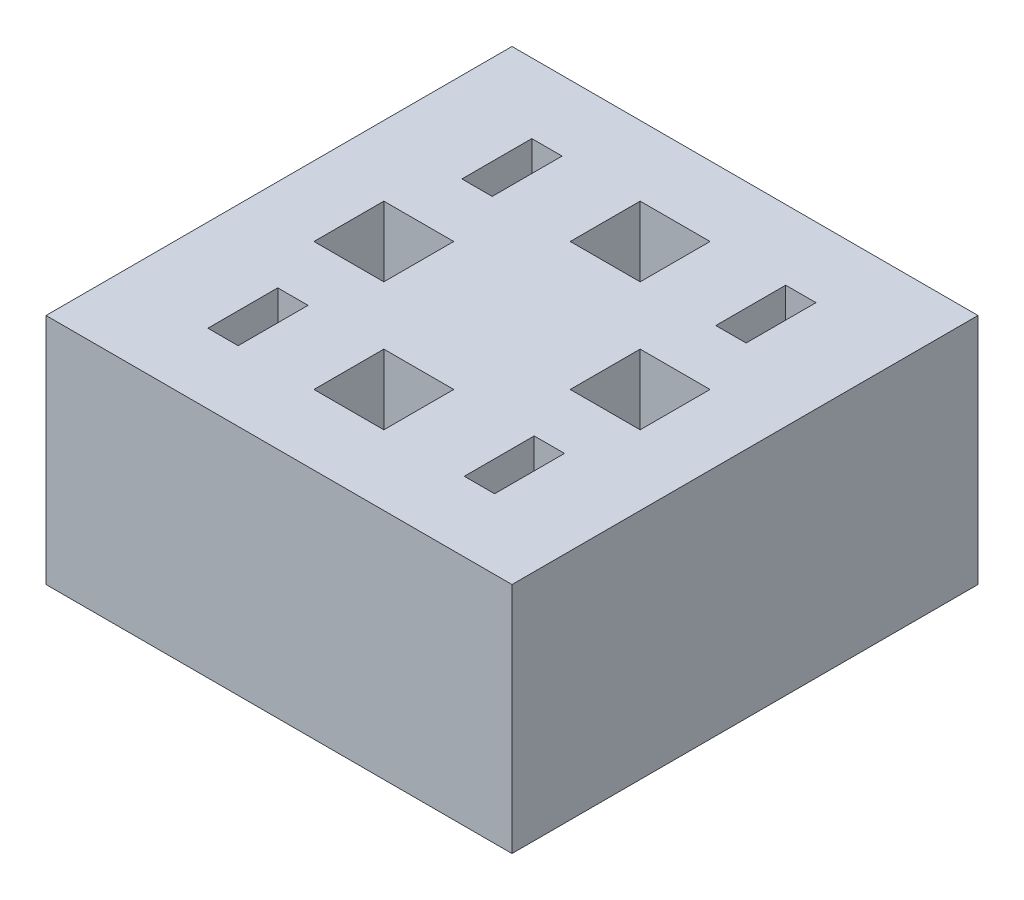
SolidWorks part; units mm, degrees
ref_plane "Спереди" through (0, 0, 0) normal (0, 0, 1) x (1, 0, 0)
ref_plane "Сверху" through (0, 0, 0) normal (0, 1, 0) x (1, 0, 0)
ref_plane "Справа" through (0, 0, 0) normal (1, 0, 0) x (0, 0, -1)
sketch "дырки" plane through (0, 0, 0) normal (0, 1, 0) x (1, 0, 0)
  line L0 (8, -3) -> (14, -3)
  line L1 (-14, -3) -> (-8, -3)
  line L2 (-14, -3) -> (-14, 3)
  line L3 (-14, 3) -> (-8, 3)
  line L4 (-8, -3) -> (-8, 3)
  line L5 (-14, -3) -> (-8, 3) construction
  line L6 (-14, 3) -> (-8, -3) construction
  line L7 (8, -3) -> (8, 3)
  line L8 (8, 3) -> (14, 3)
  line L9 (14, -3) -> (14, 3)
  line L10 (8, -3) -> (14, 3) construction
  line L11 (8, 3) -> (14, -3) construction
  line L12 (-3, -14) -> (3, -14)
  line L13 (-3, -14) -> (-3, -8)
  line L14 (-3, -8) -> (3, -8)
  line L15 (3, -14) -> (3, -8)
  line L16 (-3, -14) -> (3, -8) construction
  line L17 (-3, -8) -> (3, -14) construction
  line L18 (-3, 8) -> (3, 8)
  line L19 (-3, 8) -> (-3, 14)
  line L20 (-3, 14) -> (3, 14)
  line L21 (3, 8) -> (3, 14)
  line L22 (-3, 8) -> (3, 14) construction
  line L23 (-3, 14) -> (3, 8) construction
  line L24 (0, 8) -> (0, 0) construction
  line L25 (0, 0) -> (8, 0) construction
  line L26 (0, 0) -> (0, -8) construction
  line L27 (0, 0) -> (-8, 0) construction
  line L29 (-20, -20) -> (20, -20)
  line L30 (-20, -20) -> (-20, 20)
  line L31 (-20, 20) -> (20, 20)
  line L32 (20, -20) -> (20, 20)
  line L33 (-20, -20) -> (20, 20) construction
  line L34 (-20, 20) -> (20, -20) construction
  point P0 (-11, 0)
  point P5 (11, 0)
  point P11 (0, -11)
  point P16 (0, 11)
  dimension "D1" = 6
  dimension "D2" = 8
  dimension "D3" = 40
extrude "Бобышка-Вытянуть1" add sketch "дырки" along normal blind 10
sketch "Эскиз1" plane through (0, 0, 0) normal (0, -1, 0) x (1, 0, 0)
  line L0 (0, 14) -> (0, -14) construction
  line L1 (-20, 20) -> (20, 20)
  line L2 (-20, 20) -> (-20, -20)
  line L3 (-20, -20) -> (20, -20)
  line L4 (20, 20) -> (20, -20)
  line L5 (-3, 14) -> (3, 14) construction
  line L6 (3, -14) -> (-3, -14) construction
  line L8 (-14, 0) -> (14, 0) construction
  line L9 (-14, -3) -> (-14, 3) construction
  line L10 (14, 3) -> (14, -3) construction
  line L12 (-11, 3) -> (-11, -3) construction
  line L13 (-14, 3) -> (-8, 3) construction
  line L14 (-8, -3) -> (-14, -3) construction
  line L15 (-3, 11) -> (3, 11) construction
  line L16 (-3, 8) -> (-3, 14) construction
  line L17 (3, 14) -> (3, 8) construction
  line L19 (11, 3) -> (11, -3) construction
  line L20 (8, 3) -> (14, 3) construction
  line L21 (14, -3) -> (8, -3) construction
  line L23 (-3, -11) -> (3, -11) construction
  line L24 (-3, -14) -> (-3, -8) construction
  line L25 (3, -8) -> (3, -14) construction
  line L27 (-5, 14.5) -> (5, 14.5)
  line L28 (-5, 14.5) -> (-5, 7.5)
  line L29 (-5, 7.5) -> (5, 7.5)
  line L30 (5, 14.5) -> (5, 7.5)
  line L31 (0, 7.5) -> (0, 14.5) construction
  line L32 (-5, 11) -> (5, 11) construction
  line L33 (-1.5, 7.5) -> (1.5, 7.5)
  line L34 (-1.5, 7.5) -> (-1.5, 14.5)
  line L35 (-1.5, 14.5) -> (1.5, 14.5)
  line L36 (1.5, 7.5) -> (1.5, 14.5)
  line L37 (0, 14.5) -> (0, 7.5) construction
  line L38 (-1.5, 11) -> (1.5, 11) construction
  line L39 (-5, -14.5) -> (5, -14.5)
  line L40 (-5, -14.5) -> (-5, -7.5)
  line L41 (-5, -7.5) -> (5, -7.5)
  line L42 (5, -14.5) -> (5, -7.5)
  line L43 (0, -7.5) -> (0, -14.5) construction
  line L44 (-5, -11) -> (5, -11) construction
  line L45 (-1.5, -14.5) -> (1.5, -14.5)
  line L46 (-1.5, -14.5) -> (-1.5, -7.5)
  line L47 (-1.5, -7.5) -> (1.5, -7.5)
  line L48 (1.5, -14.5) -> (1.5, -7.5)
  line L49 (0, -7.5) -> (0, -14.5) construction
  line L50 (-1.5, -11) -> (1.5, -11) construction
  line L51 (7.5, 5) -> (14.5, 5)
  line L52 (7.5, 5) -> (7.5, -5)
  line L53 (7.5, -5) -> (14.5, -5)
  line L54 (14.5, 5) -> (14.5, -5)
  line L55 (11, -5) -> (11, 5) construction
  line L56 (7.5, 0) -> (14.5, 0) construction
  line L57 (14.5, -1.5) -> (7.5, -1.5)
  line L58 (14.5, -1.5) -> (14.5, 1.5)
  line L59 (14.5, 1.5) -> (7.5, 1.5)
  line L60 (7.5, -1.5) -> (7.5, 1.5)
  line L61 (11, 1.5) -> (11, -1.5) construction
  line L62 (14.5, 0) -> (7.5, 0) construction
  line L63 (-14.5, -5) -> (-7.5, -5)
  line L64 (-14.5, -5) -> (-14.5, 5)
  line L65 (-14.5, 5) -> (-7.5, 5)
  line L66 (-7.5, -5) -> (-7.5, 5)
  line L67 (-11, 5) -> (-11, -5) construction
  line L68 (-14.5, 0) -> (-7.5, 0) construction
  line L69 (-14.5, -1.5) -> (-7.5, -1.5)
  line L70 (-14.5, -1.5) -> (-14.5, 1.5)
  line L71 (-14.5, 1.5) -> (-7.5, 1.5)
  line L72 (-7.5, -1.5) -> (-7.5, 1.5)
  line L73 (-11, 1.5) -> (-11, -1.5) construction
  line L74 (-14.5, 0) -> (-7.5, 0) construction
  line L75 (9.9066, 8) -> (12.5066, 8)
  line L76 (9.9066, 8) -> (9.9066, 14)
  line L77 (9.9066, 14) -> (12.5066, 14)
  line L78 (12.5066, 8) -> (12.5066, 14)
  line L79 (11.2066, 14) -> (11.2066, 8) construction
  line L80 (9.9066, 11) -> (12.5066, 11) construction
  line L81 (-12.1066, 8) -> (-9.5066, 8)
  line L82 (-12.1066, 8) -> (-12.1066, 14)
  line L83 (-12.1066, 14) -> (-9.5066, 14)
  line L84 (-9.5066, 8) -> (-9.5066, 14)
  line L85 (-10.8066, 14) -> (-10.8066, 8) construction
  line L86 (-12.1066, 11) -> (-9.5066, 11) construction
  line L87 (-12.3, -14) -> (-9.7, -14)
  line L88 (-12.3, -14) -> (-12.3, -8)
  line L89 (-12.3, -8) -> (-9.7, -8)
  line L90 (-9.7, -14) -> (-9.7, -8)
  line L91 (-11, -8) -> (-11, -14) construction
  line L92 (-12.3, -11) -> (-9.7, -11) construction
  line L93 (9.4934, -14) -> (12.0934, -14)
  line L94 (9.4934, -14) -> (9.4934, -8)
  line L95 (9.4934, -8) -> (12.0934, -8)
  line L96 (12.0934, -14) -> (12.0934, -8)
  line L97 (10.7934, -8) -> (10.7934, -14) construction
  line L98 (9.4934, -11) -> (12.0934, -11) construction
  point P42 (0, 11)
  point P46 (0, 11)
  point P50 (0, -11)
  point P54 (0, -11)
  point P58 (11, 0)
  point P62 (11, 0)
  point P66 (-11, 0)
  point P70 (-11, 0)
  point P74 (11.2066, 11)
  point P78 (-10.8066, 11)
  point P82 (-11, -11)
  point P86 (10.7934, -11)
  line M13 (20, -20) -> (20, 20)
  line M14 (20, 20) -> (-20, 20)
  line M15 (-20, 20) -> (-20, -20)
  line M16 (-20, -20) -> (20, -20)
  dimension "D1" = 10
  dimension "D2" = 7
  dimension "D3" = 3
  dimension "D4" = 3
  dimension "D5" = 3
  dimension "D6" = 3
  dimension "D7" = 6
  dimension "D8" = 2.6
extrude "Бобышка-Вытянуть5" add sketch "Эскиз1" along normal blind 10 contours L96 L93 L94 L95 L90 L87 L88 L89 L84 L81 L82 L83 L78 L75 L76 L77 L66 L63 L64 L65 L27 L30 L29 L28 L42 L39 L40 L41 M16 M13 M14 M15 | L84 L83 L82 L81 | L78 L77 L76 L75 | L96 L95 L94 L93 | L90 L89 L88 L87 | L48 L47 L46 L45 | L57 L60 L59 L58 | L69 L72 L71 L70 | L36 L35 L34 L33 region at (-0.0024, 0, 0)
extrude "Вырез-Вытянуть1" cut sketch "Эскиз1<6>" against normal through all both and the other way through all contours L84 L83 L82 L81
sketch "Эскиз1<6>" plane through (0, 0, 0) normal (0, -1, 0) x (1, 0, 0) same geometry as "Эскиз1"
extrude "Вырез-Вытянуть2" cut sketch "Эскиз1<7>" against normal through all both and the other way through all contours L78 L77 L76 L75
sketch "Эскиз1<7>" plane through (0, 0, 0) normal (0, -1, 0) x (1, 0, 0) same geometry as "Эскиз1"
extrude "Вырез-Вытянуть3" cut sketch "Эскиз1<8>" against normal through all both and the other way through all contours L96 L95 L94 L93
sketch "Эскиз1<8>" plane through (0, 0, 0) normal (0, -1, 0) x (1, 0, 0) same geometry as "Эскиз1"
extrude "Вырез-Вытянуть4" cut sketch "Эскиз1<9>" against normal through all both and the other way through all contours L90 L89 L88 L87
sketch "Эскиз1<9>" plane through (0, 0, 0) normal (0, -1, 0) x (1, 0, 0) same geometry as "Эскиз1"
